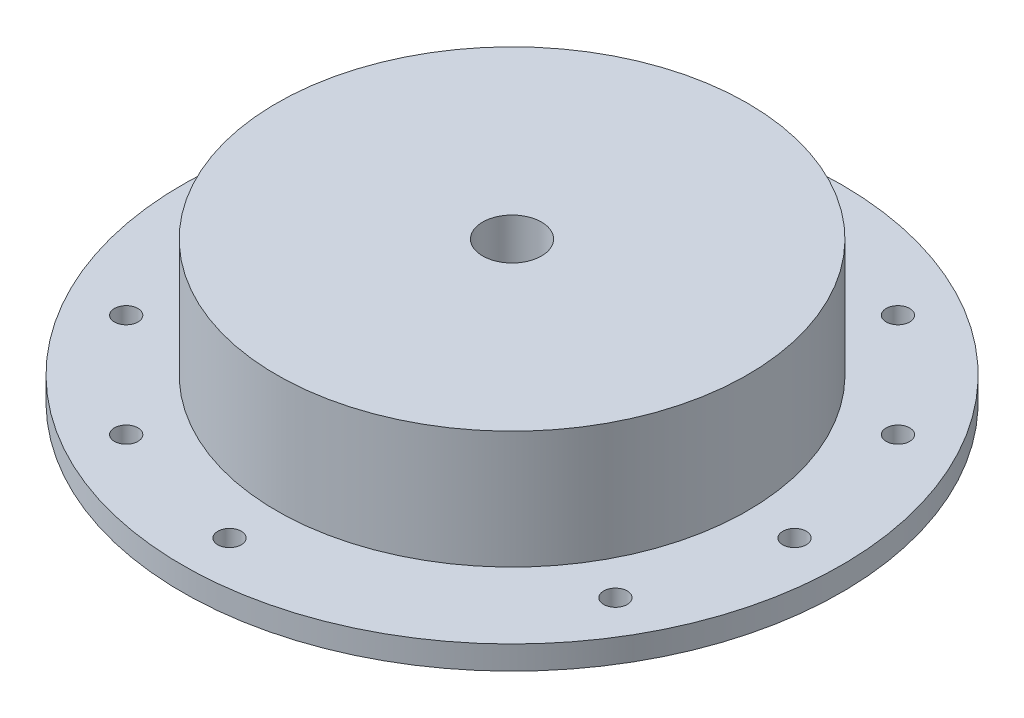
SolidWorks part; units mm, degrees
material "AISI 316 Annealed Stainless Steel Bar (SS)"
ref_plane "Front Plane" through (0, 0, 0) normal (0, 0, 1) x (1, 0, 0)
ref_plane "Top Plane" through (0, 0, 0) normal (0, 1, 0) x (1, 0, 0)
ref_plane "Right Plane" through (0, 0, 0) normal (1, 0, 0) x (0, 0, -1)
sketch "Sketch1" plane through (0, 0, 0) normal (0, 0, 1) x (1, 0, 0)
  line L0 (7.9375, 38.1) -> (7.9375, 11.1125)
  line L1 (38.1, 0) -> (88.9, 0)
  line L2 (88.9, 0) -> (88.9, 6.35)
  line L3 (88.9, 6.35) -> (63.5, 6.35)
  line L4 (63.5, 6.35) -> (63.5, 38.1)
  line L5 (63.5, 38.1) -> (7.9375, 38.1)
  line L6 (0, 0) -> (0, 33.4189) construction
  arc A0 (7.9375, 11.1125) -> (38.1, 0) centre (38.1, 46.4911) ccw
  dimension "D1" = 15.875
  dimension "D2" = 177.8
  dimension "D3" = 25.4
  dimension "D4" = 6.35
  dimension "D5" = 38.1
  dimension "D6" = 76.2
  dimension "D7" = 11.1125
revolve "Revolve1" add sketch "Sketch1" angle 360 about L6
sketch "Sketch3" plane through (0, 6.35, 0) normal (0, 1, 0) x (1, 0, 0)
  line L0 (0, 0) -> (0, -101.6) construction
  point P4 (0, -101.6)
  dimension "D1" = 101.6
hole_wizard "1/4 (0.25) Diameter Hole1" positions "Sketch4" profile "Sketch5" hole size "1/4" standard "ANSI Inch" end condition through all
sketch "Sketch4" plane through (0, 6.35, 0) normal (0, 1, 0) x (1, 0, 0)
  line L2 (0, 0) -> (0, -76.2) construction
  point P0 (0, -76.2)
  dimension "D1" = 76.2
sketch "Sketch5" plane through (0, 6.35, 76.2) normal (1, 0, 0) x (0, 0, 1)
  line L0 (0, 0) -> (0, 6.35)
  line L1 (0, 6.35) -> (3.175, 6.35)
  line L2 (3.175, 6.35) -> (3.175, 0)
  line L5 (3.175, 0) -> (0, 0)
  line L11 (0, -6.35) -> (0, 107.95) construction
  dimension "Thru Hole Dia." = 6.35
  dimension "Thru Hole Depth" = 6.35
pattern_circular "CirPattern2" count 12 over 360 about axis through (0, 0, 0) along (0, -1, 0) skipping 1 of "1/4 (0.25) Diameter Hole1" reverse direction yes
